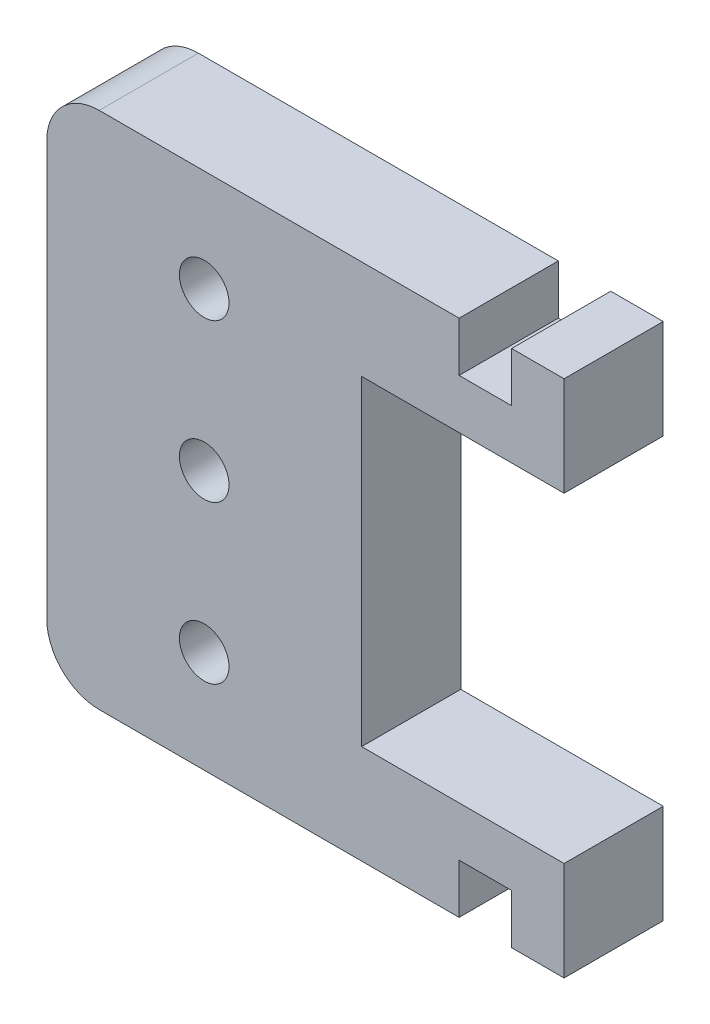
SolidWorks part; units mm, degrees
ref_plane "Front Plane" through (0, 0, 0) normal (0, 0, 1) x (1, 0, 0)
ref_plane "Top Plane" through (0, 0, 0) normal (0, 1, 0) x (1, 0, 0)
ref_plane "Right Plane" through (0, 0, 0) normal (1, 0, 0) x (0, 0, -1)
sketch "Sketch1" plane through (0, 0, 0) normal (0, 0, 1) x (1, 0, 0)
  line L0 (15.425, -15.7) -> (15.425, -12.7)
  line L1 (-9.525, -15.7) -> (9.525, -15.7)
  line L2 (-9.525, -15.7) -> (-9.525, 15.7)
  line L3 (-9.525, 15.7) -> (9.525, 15.7)
  line L4 (9.525, -15.7) -> (9.525, 15.7)
  line L5 (-9.525, -15.7) -> (9.525, 15.7) construction
  line L6 (-9.525, 15.7) -> (9.525, -15.7) construction
  line L7 (21.775, 9.7) -> (9.525, 9.7)
  line L8 (21.775, 9.7) -> (21.775, 15.7)
  line L9 (21.775, 15.7) -> (9.525, 15.7)
  line L10 (9.525, 9.7) -> (9.525, 15.7)
  line L11 (21.775, -9.7) -> (9.525, -9.7)
  line L12 (21.775, -9.7) -> (21.775, -15.7)
  line L13 (21.775, -15.7) -> (9.525, -15.7)
  line L14 (9.525, -9.7) -> (9.525, -15.7)
  line L15 (15.425, -12.7) -> (18.6, -12.7)
  line L16 (18.6, -12.7) -> (18.6, -15.7)
  line L17 (15.425, 15.7) -> (15.425, 12.7)
  line L18 (15.425, 12.7) -> (18.6, 12.7)
  line L19 (18.6, 12.7) -> (18.6, 15.7)
  point P0 (0, 0)
  dimension "D1" = 31.4
  dimension "D2" = 19.05
  dimension "D3" = 5.9
  dimension "D4" = 3.175
  dimension "D5" = 3.175
  dimension "D6" = 3
  dimension "D7" = 6
extrude "Boss-Extrude1" add sketch "Sketch1" along normal mid plane 6 contours L1 L4 L3 L2 | L19 L18 L17 L9 L4 L7 L8 | L15 L16 L13 L12 L11 L4 L0 region at (15.4471, -12.4767, 0) region at (0, 0, 0) region at (15.4471, 12.4767, 0)
fillet "Fillet1" radius 3.175 2 edges at (-9.525, -15.7, 0) (-9.525, 15.7, 0)
sketch "Sketch2" plane through (0, 0, 3) normal (0, 0, 1) x (1, 0, 0)
  line L0 (9.525, -9.7) -> (9.525, 9.7) construction
  line L1 (0, 9.525) -> (0, -9.525) construction
  circle A0 centre (0, 9.525) radius 1.5
  circle A1 centre (0, -9.525) radius 1.5
  circle A2 centre (0, 0) radius 1.5
  point P4 (0, 0)
  dimension "D1" = 3
  dimension "D2" = 9.525
  dimension "D3" = 19.05
extrude "Cut-Extrude1" cut sketch "Sketch2" against normal through all both and the other way through all
equation "\"D1@Sketch1\"=1in+6mm"
